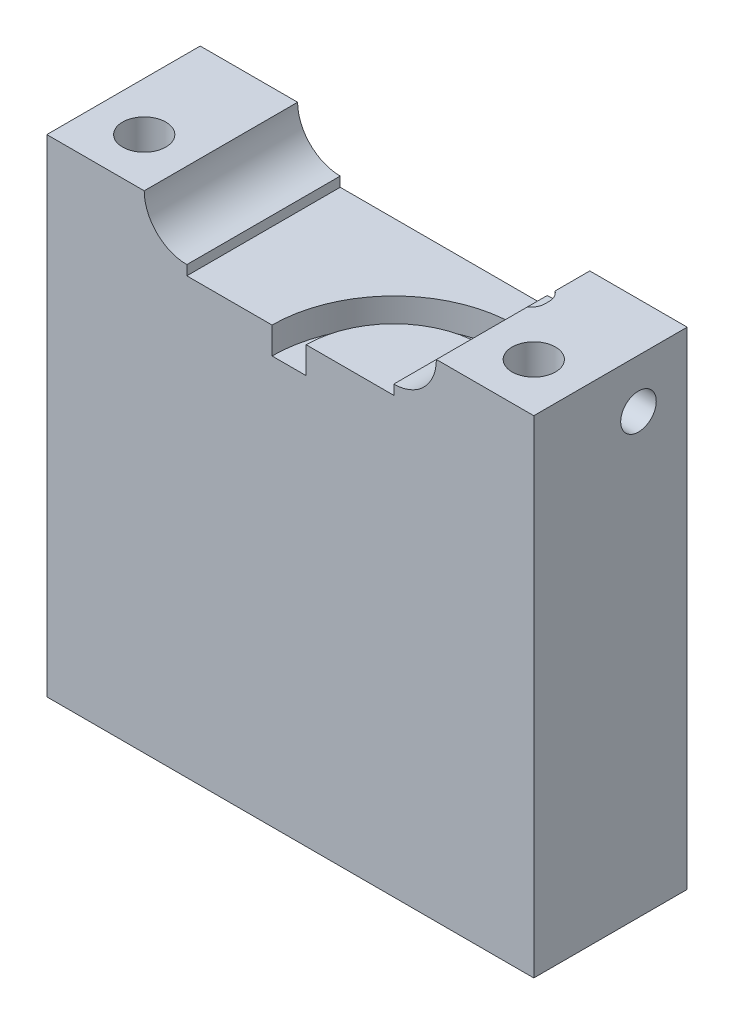
SolidWorks part; units mm, degrees
ref_plane "Front Plane" through (0, 0, 0) normal (0, 0, 1) x (1, 0, 0)
ref_plane "Top Plane" through (0, 0, 0) normal (0, 1, 0) x (1, 0, 0)
ref_plane "Right Plane" through (0, 0, 0) normal (1, 0, 0) x (0, 0, -1)
sketch "Sketch1" plane through (0, 0, 0) normal (0, 1, 0) x (1, 0, 0)
  line L1 (-12.7, -4.0005) -> (12.7, -4.0005)
  line L2 (-12.7, -4.0005) -> (-12.7, 4.0005)
  line L3 (-12.7, 4.0005) -> (12.7, 4.0005)
  line L4 (12.7, -4.0005) -> (12.7, 4.0005)
  line L5 (-12.7, -4.0005) -> (12.7, 4.0005) construction
  line L6 (-12.7, 4.0005) -> (12.7, -4.0005) construction
  point P0 (0, 0)
  dimension "D1" = 25.4
  dimension "D2" = 8.001
extrude "Boss-Extrude1" add sketch "Sketch1" along normal blind 25.4
sketch "Sketch2" plane through (0, 0, -4.0005) normal (0, 0, -1) x (-1, 0, 0)
  line L0 (5.3975, 25.4) -> (-5.3975, 25.4) construction
  line L1 (5.3975, 23.1775) -> (-5.3975, 23.1775)
  line L2 (5.3975, 27.6225) -> (-5.3975, 27.6225)
  line L3 (12.7, 25.4) -> (-12.7, 25.4) construction
  line L5 (-12.7, 25.4) -> (12.7, 25.4) construction
  line L6 (12.7, 25.4) -> (12.7, 0) construction
  line L7 (-12.7, 25.4) -> (-12.7, 0) construction
  arc A0 (5.3975, 23.1775) -> (5.3975, 27.6225) centre (5.3975, 25.4) ccw
  arc A1 (-5.3975, 27.6225) -> (-5.3975, 23.1775) centre (-5.3975, 25.4) ccw
  point P2 (0, 25.4)
  dimension "D2" = 10.795
  dimension "D3" = 4.445
extrude "Cut-Extrude1" cut sketch "Sketch2" against normal blind 25.4
ref_plane "Plane1" through (0, 23.1775, 0) normal (0, 1, 0) x (1, 0, 0)
sketch "Sketch4" plane through (0, 23.1775, 0) normal (0, 1, 0) x (1, 0, 0)
  line L0 (0, -9.1985) -> (0, 12.0201) construction
  line L1 (0.8255, -4.0005) -> (-0.9525, -4.0005)
  line L2 (5.3975, 0.5715) -> (7.1437, 0.5715)
  line L3 (7.9375, 1.3652) -> (7.9375, 1.5557)
  line L4 (7.1437, 2.3495) -> (5.3975, 2.3495)
  arc A0 (5.3975, 2.3495) -> (-0.9525, -4.0005) centre (5.3975, -4.0005) ccw
  arc A1 (5.3975, 0.5715) -> (0.8255, -4.0005) centre (5.3975, -4.0005) ccw
  arc A2 (7.9375, 1.3652) -> (7.1437, 0.5715) centre (7.1437, 1.3652) cw
  arc A3 (7.9375, 1.5557) -> (7.1437, 2.3495) centre (7.1437, 1.5557) ccw
  dimension "D1" = 12.7
  dimension "D2" = 9.144
  dimension "D3" = 2.54
  dimension "D4" = 0.7937
extrude "Cut-Extrude2" cut sketch "Sketch4" against normal blind 1.905 and the other way through all
ref_plane "Plane3" through (12.7, 0, 0) normal (1, 0, 0) x (0, 0, -1)
sketch "Sketch5" plane through (12.7, 0, 0) normal (1, 0, 0) x (0, 0, -1)
  line L0 (-4.0005, 25.4) -> (-4.0005, 0) construction
  line L1 (-4.0005, 25.4) -> (4.0005, 25.4) construction
  circle A0 centre (1.4605, 22.86) radius 0.9271
  dimension "D2" = 1.8542
  dimension "D1" = 5.461
  dimension "D3" = 2.54
extrude "Cut-Extrude3" cut sketch "Sketch5" against normal blind 6.35
sketch "Sketch6" plane through (0, 23.1775, 0) normal (0, 1, 0) x (1, 0, 0)
  line L1 (-5.3975, 4.0005) -> (5.3975, 4.0005)
  line L2 (-5.3975, 4.0005) -> (-5.3975, -4.0005)
  line L3 (-5.3975, -4.0005) -> (5.3975, -4.0005)
  line L4 (5.3975, 4.0005) -> (5.3975, -4.0005)
extrude "Cut-Extrude4" cut sketch "Sketch6" against normal blind 0.508
hole_wizard "#4-40 Tapped Hole1" positions "Sketch8" profile "Sketch7" tap size "#4-40" standard "ANSI Inch"
sketch "Sketch8" plane through (0, 25.4, 0) normal (0, 1, 0) x (1, 0, 0)
  line L0 (-12.7, -4.0005) -> (-7.62, -4.0005) construction
  line L1 (-12.7, 4.0005) -> (-12.7, -4.0005) construction
  line L2 (12.7, -4.0005) -> (12.7, 4.0005) construction
  point P0 (-10.16, -1.4605)
  point P2 (10.16, -1.4605)
  dimension "D1" = 2.54
  dimension "D2" = 2.54
  dimension "D3" = 2.54
sketch "Sketch7" plane through (-10.16, 25.4, 1.4605) normal (1, 0, 0) x (0, 0, 1)
  line L0 (0, 0) -> (0, 11.6012)
  line L1 (0, 11.6012) -> (1.1303, 10.922)
  line L2 (1.1303, 10.922) -> (1.1303, 0)
  line L5 (1.1303, 0) -> (0, 0)
  line L10 (0, 11.6012) -> (-1.1303, 10.922) construction
  line L11 (0, -6.35) -> (0, 107.95) construction
  dimension "Tap Drill Dia." = 2.2606
  dimension "Tap Drill Depth" = 10.922
  dimension "Drill Angle" = 118
